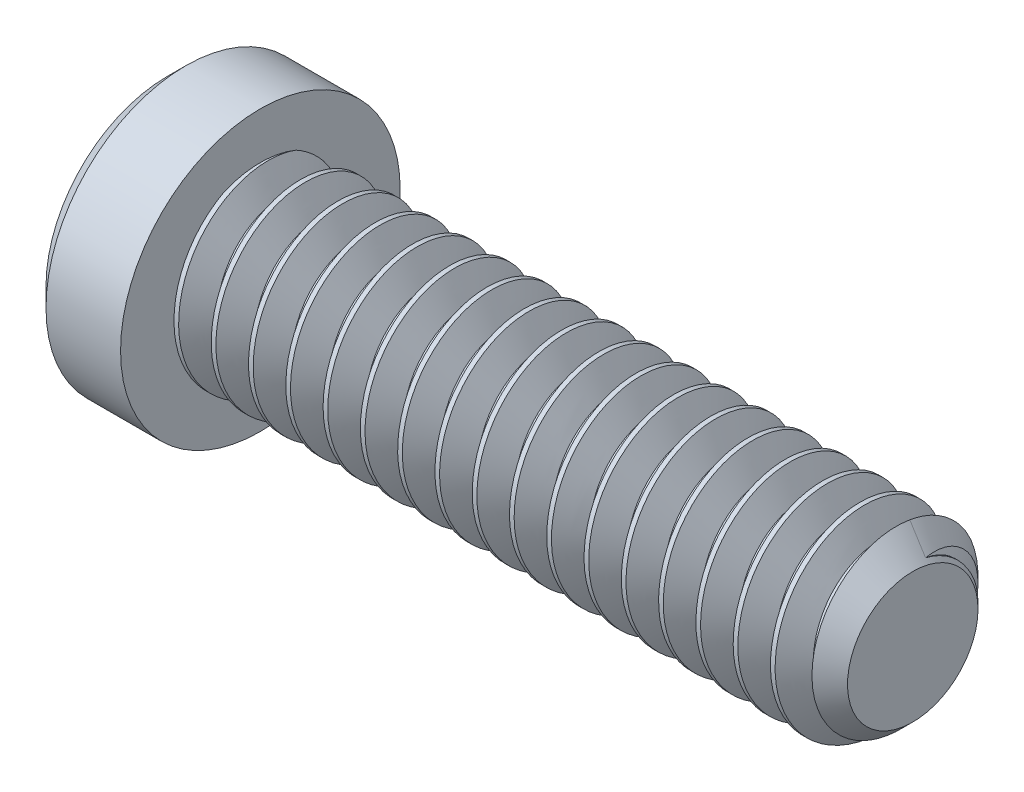
SolidWorks part; units mm, degrees
ref_plane "Front Plane" through (0, 0, 0) normal (0, 0, 1) x (1, 0, 0)
ref_plane "Top Plane" through (0, 0, 0) normal (0, 1, 0) x (1, 0, 0)
ref_plane "Right Plane" through (0, 0, 0) normal (1, 0, 0) x (0, 0, -1)
sketch "Sketch1" plane through (0, 0, 0) normal (0, 0, 1) x (1, 0, 0)
  line L0 (11.1125, 0) -> (-11.1125, 0) construction
  line L1 (11.1125, 3.175) -> (11.1125, -3.175) construction
  line L2 (-11.1125, 4.7625) -> (-11.1125, -4.7625) construction
  line L3 (-11.1125, 4.7625) -> (-13.6525, 4.7625) construction
  line L4 (-13.6525, 4.7625) -> (-14.2875, 4.1275) construction
  line L5 (-14.2875, 4.1275) -> (-14.2875, -4.1275) construction
  line L6 (-14.2875, -4.1275) -> (-13.6525, -4.7625) construction
  line L7 (-13.6525, -4.7625) -> (-11.1125, -4.7625) construction
  point P7 (-11.8999, 0)
  point P12 (6.0325, -3.175)
  dimension "D1" = 45
  dimension "D2" = 5.08
  dimension "Dec." = 6.35
  dimension "Length" = 22.225
  dimension "Head Dia" = 9.525
  dimension "Head Height" = 3.175
  dimension "Hex Depth" = 2.3876
  dimension "Chamfer" = 0.635
ref_plane "Plane1" through (11.1125, 0, 0) normal (1, 0, 0) x (0, 0, -1)
ref_plane "Plane2" through (-14.2875, 0, 0) normal (1, 0, 0) x (0, 0, -1)
sketch "Sketch2" plane through (11.1125, 0, 0) normal (1, 0, 0) x (0, 0, -1)
  circle A0 centre (0, 0) radius 3.175
extrude "Boss-Extrude1" add sketch "Sketch2" against normal up to vertex (22.225 mm away) up to point (-11.1125, 0, 0)
sketch "Sketch3" plane through (11.1125, 0, 0) normal (1, 0, 0) x (0, 0, -1)
  circle A0 centre (0, 0) radius 3.175 construction
  circle A1 centre (0, 0) radius 3.175
curve "Helix/Spiral1" pitch 1.27 height 23.495 radius 3.175 centre (11.1125, 0, 0) axis (-1, 0, 0) start towards (0, 1, 0) parameters "Pitch"=1.27
chamfer "Chamfer1" distance 0.9525 angle 45 1 edges at (11.1125, 0, -3.175)
sketch "Sketch5" plane through (0, 0, 0) normal (0, 0, 1) x (1, 0, 0)
  line L0 (10.5569, 3.175) -> (11.6681, 3.175)
  line L1 (11.6681, 3.175) -> (11.1919, 2.3501)
  line L2 (11.1919, 2.3501) -> (11.0331, 2.3501)
  line L3 (11.0331, 2.3501) -> (10.5569, 3.175)
  line L4 (11.1125, 2.3501) -> (11.1125, 3.175) construction
  line L5 (10.795, 2.7626) -> (11.43, 2.7626) construction
  dimension "D1" = 60
  dimension "D2" = 0.635
  dimension "D3" = 0.1588
sweep "Cut-Sweep1" cut profiles "Sketch5" path "Helix/Spiral1"
sketch "Sketch4" plane through (-14.2875, 0, 0) normal (1, 0, 0) x (0, 0, -1)
  line L0 (-4.7625, 0.7937) -> (4.7625, 0.7937) construction
  line L1 (0, 1.8331) -> (-1.5875, 0.9165)
  line L2 (-1.5875, 0.9165) -> (-1.5875, -0.9165)
  line L3 (-1.5875, -0.9165) -> (0, -1.8331)
  line L4 (0, -1.8331) -> (1.5875, -0.9165)
  line L5 (1.5875, -0.9165) -> (1.5875, 0.9165)
  line L6 (1.5875, 0.9165) -> (0, 1.8331)
  line L7 (0, 0) -> (0, 0.7937) construction
  circle A0 centre (0, 0) radius 1.5875 construction
  dimension "D1" = 9.525
  dimension "Hex Size" = 3.175
  dimension "D2" = 0.7937
sketch "Sketch6" plane through (0, 0, 0) normal (0, 0, 1) x (1, 0, 0)
  line L0 (-13.6525, 4.7625) -> (-14.2875, 4.1275) construction
  line L1 (-11.1125, 4.7625) -> (-13.6525, 4.7625) construction
  line L2 (-11.1125, 4.7625) -> (-11.1125, -4.7625) construction
  line L3 (-14.2875, 4.1275) -> (-14.2875, -4.1275) construction
  line L4 (-13.6525, 4.7625) -> (-14.2875, 4.1275)
  line L5 (-11.1125, 4.7625) -> (-13.6525, 4.7625)
  line L6 (-11.1125, 4.7625) -> (-11.1125, 0)
  line L7 (-14.2875, 4.1275) -> (-14.2875, 0)
  line L8 (-11.1125, 0) -> (-14.2875, 0) construction
  line L9 (-11.1125, 0) -> (-14.2875, 0)
revolve "Revolve1" add sketch "Sketch6" angle 360 about L8
extrude "Cut-Extrude1" cut sketch "Sketch4" along normal up to vertex (2.3876 mm away) up to point (-11.8999, 0, 0)
sketch "Sketch8" plane through (-14.2875, 0, 0) normal (-1, 0, 0) x (0, 0, 1)
  circle A1 centre (0, 0) radius 1.8331
extrude "Cut-Extrude2" cut sketch "Sketch8" against normal through all draft 45
equation "\"D3@Helix/Spiral1\" = \"Length@Sketch1\"+\"Pitch@Helix/Spiral1\""
equation "\"D3@Sketch5\" = \"Pitch@Helix/Spiral1\"*.125"
equation "\"D2@Sketch5\" = \"Pitch@Helix/Spiral1\"*.50"
equation "\"D1@Chamfer1\" = \"Pitch@Helix/Spiral1\"*.75"
equation "\"D2@Sketch1\" = \"Pitch@Helix/Spiral1\"*4"
equation "\"D1@Sketch4\" = \"Head Dia@Sketch1\""
